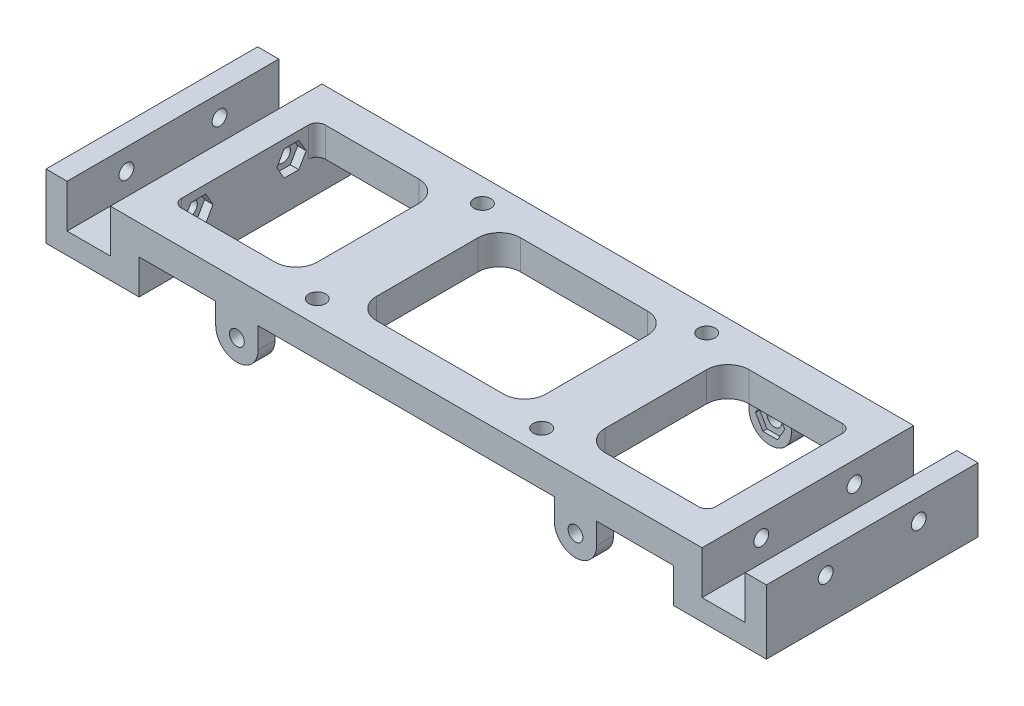
SolidWorks part; units mm, degrees
note: The reader was unsure of these and kept them because the rebuilt part matched: shared geometry of "Szkic5<2>".
material "ABS"
ref_plane "Płaszczyzna przednia" through (0, 0, 0) normal (0, 0, 1) x (1, 0, 0)
ref_plane "Płaszczyzna górna" through (0, 0, 0) normal (0, 1, 0) x (1, 0, 0)
ref_plane "Płaszczyzna prawa" through (0, 0, 0) normal (1, 0, 0) x (0, 0, -1)
sketch "Szkic1" plane through (0, 0, 0) normal (0, 0, 1) x (1, 0, 0)
  line L0 (0, 0) -> (0, 47.3092) construction
  line L1 (-80.1, 5.1) -> (-69.9, 5.1)
  line L2 (-80.1, 5.1) -> (-80.1, -5.1)
  line L3 (-80.1, -5.1) -> (-69.9, -5.1)
  line L4 (-69.9, 5.1) -> (-69.9, -5.1)
  line L5 (-80.1, 5.1) -> (-69.9, -5.1) construction
  line L6 (-80.1, -5.1) -> (-69.9, 5.1) construction
  line L7 (69.8998, 5.1002) -> (80.1002, 5.1002)
  line L8 (69.8998, 5.1002) -> (69.8998, -5.1002)
  line L9 (69.8998, -5.1002) -> (80.1002, -5.1002)
  line L10 (80.1002, 5.1002) -> (80.1002, -5.1002)
  line L11 (69.8998, 5.1002) -> (80.1002, -5.1002) construction
  line L12 (69.8998, -5.1002) -> (80.1002, 5.1002) construction
  line L13 (-80.1, 5.1) -> (-85.1, 5.1)
  line L14 (-85.1, 5.1) -> (-85.1, -10.1)
  line L15 (-85.1, -10.1) -> (85.1, -10.1)
  line L16 (85.1, -10.1) -> (85.1, 5.1002)
  line L17 (85.1, 5.1002) -> (80.1002, 5.1002)
  line L18 (-69.9, 5.1) -> (69.8998, 5.1002)
  line L19 (-63.1, -10.1) -> (-63.1, -1.9)
  line L20 (-63.1, -1.9) -> (63.1, -1.9)
  line L21 (63.1, -1.9) -> (63.1, -10.1)
  point P0 (-75, 0)
  point P5 (75, 0)
  dimension "D1" = 10.2
  dimension "D2" = 10.2004
  dimension "D3" = 150
  dimension "D4" = 4.9998
  dimension "D5" = 5
  dimension "D6" = 5
  dimension "D7" = 22
  dimension "D8" = 22
  dimension "D9" = 8.2
extrude "Dodanie-wyciągnięcie1" add sketch "Szkic1" along normal blind 50
sketch "Szkic2" plane through (0, -10.1, 0) normal (0, -1, 0) x (1, 0, 0)
  line L0 (85.1, 25) -> (-85.1, 25) construction
  line L1 (85.1, 50) -> (85.1, 0) construction
  line L2 (-85.1, 50) -> (-85.1, 0) construction
  line L3 (0, 0) -> (0, 66.8326) construction
  circle A0 centre (-26.5, 44.5) radius 2
  circle A1 centre (-26.5, 5.5) radius 2
  circle A2 centre (26.5, 5.5) radius 2
  circle A3 centre (26.5, 44.5) radius 2
  point P10 (24.4989, 5.5)
  dimension "D1" = 4
  dimension "D2" = 39
  dimension "D3" = 53
extrude "Wytnij-wyciągnięcie1" cut sketch "Szkic2" against normal blind 35
sketch "Szkic3" plane through (0, -10.1, 0) normal (0, -1, 0) x (1, 0, 0)
  line L0 (85.1, 25) -> (-85.1, 25) construction
  line L1 (-20, 42) -> (20, 42)
  line L2 (-20, 42) -> (-20, 8)
  line L3 (-20, 8) -> (20, 8)
  line L4 (20, 42) -> (20, 8)
  line L5 (-20, 42) -> (20, 8) construction
  line L6 (-20, 8) -> (20, 42) construction
  line L7 (85.1, 50) -> (85.1, 0) construction
  line L8 (-85.1, 50) -> (-85.1, 0) construction
  line L9 (0, 0) -> (0, 60.021) construction
  line L12 (-63.1, 8) -> (-34, 8)
  line L13 (-63.1, 8) -> (-63.1, 42)
  line L14 (-63.1, 42) -> (-34, 42)
  line L15 (-34, 8) -> (-34, 42)
  line L16 (-63.1, 8) -> (-34, 42) construction
  line L17 (-63.1, 42) -> (-34, 8) construction
  line L18 (34, 8) -> (63.1, 8)
  line L19 (34, 8) -> (34, 42)
  line L20 (34, 42) -> (63.1, 42)
  line L21 (63.1, 8) -> (63.1, 42)
  line L22 (34, 8) -> (63.1, 42) construction
  line L23 (34, 42) -> (63.1, 8) construction
  point P0 (0, 25)
  point P13 (0, 0)
  point P14 (0, 0)
  point P16 (48.55, 25)
  point P17 (0, 25)
  point P18 (-48.55, 25)
  dimension "D1" = 34
  dimension "D2" = 40
  dimension "D4" = 29.1
  dimension "D6" = 29.1
  dimension "D7" = 14
  dimension "D8" = 14
extrude "Wytnij-wyciągnięcie2" cut sketch "Szkic3" against normal blind 35
sketch "Szkic4" plane through (85.1, 0, 0) normal (1, 0, 0) x (0, 0, -1)
  line L0 (-25, -10.1) -> (-25, 5.1002) construction
  line L1 (-50, -10.1) -> (0, -10.1) construction
  line L2 (-50, 5.1002) -> (0, 5.1002) construction
  circle A0 centre (-36, 0.1002) radius 1.75
  circle A1 centre (-14, 0.1002) radius 1.75
  dimension "D1" = 3.5
  dimension "D2" = 22
  dimension "D3" = 5
extrude "Wytnij-wyciągnięcie3" cut sketch "Szkic4" against normal blind 35
sketch "Szkic5" plane through (85.1, 0, 0) normal (1, 0, 0) x (0, 0, -1)
  line L1 (-34.2679, 3.1002) -> (-37.7321, 3.1002)
  line L2 (-37.7321, 3.1002) -> (-39.4641, 0.1002)
  line L3 (-39.4641, 0.1002) -> (-37.7321, -2.8998)
  line L4 (-37.7321, -2.8998) -> (-34.2679, -2.8998)
  line L5 (-34.2679, -2.8998) -> (-32.5359, 0.1002)
  line L6 (-32.5359, 0.1002) -> (-34.2679, 3.1002)
  line L7 (-12.2679, 3.1002) -> (-15.7321, 3.1002)
  line L8 (-15.7321, 3.1002) -> (-17.4641, 0.1002)
  line L9 (-17.4641, 0.1002) -> (-15.7321, -2.8998)
  line L10 (-15.7321, -2.8998) -> (-12.2679, -2.8998)
  line L11 (-12.2679, -2.8998) -> (-10.5359, 0.1002)
  line L12 (-10.5359, 0.1002) -> (-12.2679, 3.1002)
  circle A0 centre (-36, 0.1002) radius 3 construction
  circle A1 centre (-14, 0.1002) radius 3 construction
  dimension "D1" = 6
extrude "Wytnij-wyciągnięcie4" cut sketch "Szkic5" along normal blind 2 from surface at -22 starting at face at (63.1, 0.1002, 34.25)
mirror "Lustro1" about plane through (0, 0, 0) normal (1, 0, 0) of "Wytnij-wyciągnięcie3"
extrude "Wytnij-wyciągnięcie5" cut sketch "Szkic5<2>" against normal blind 2 from surface at -148.2 starting at face at (-63.1, 0.1002, 37.75)
sketch "Szkic5<2>" plane through (85.1, 0, 0) normal (1, 0, 0) x (0, 0, -1) same geometry as "Szkic5"
sketch "Szkic7" plane through (0, 0, 50) normal (0, 0, 1) x (1, 0, 0)
  line L0 (-63.1, -1.9) -> (63.1, -1.9) construction
  line L3 (-34.9999, -6.9) -> (-34.9999, -1.9)
  line L4 (-44.9999, -6.9) -> (-44.9999, -1.9)
  line L5 (35.0001, -6.9) -> (35.0001, -1.9)
  line L6 (45.0001, -6.9) -> (45.0001, -1.9)
  line L7 (-63.1, -1.9) -> (63.1, -1.9)
  line L8 (0, -1.9) -> (-0.0001, 5.1001) construction
  line L9 (-69.9, 5.1) -> (69.8998, 5.1002) construction
  circle A4 centre (-39.9999, -6.9) radius 5
  circle A5 centre (40.0001, -6.9) radius 5
  circle A6 centre (-39.9999, -6.9) radius 1.75
  circle A7 centre (40.0001, -6.9) radius 1.75
  point P8 (-39.0618, -6.9)
  point P21 (0, 0)
  point P22 (0, 0)
  dimension "D1" = 10
  dimension "D3" = 5
  dimension "D4" = 5
  dimension "D5" = 80
  dimension "D2" = 3.5
  dimension "D6" = 40
extrude "Dodanie-wyciągnięcie4" add sketch "Szkic7" against normal blind 4
sketch "Szkic8" plane through (0, 0, 46) normal (0, 0, -1) x (-1, 0, 0)
  line L1 (43.464, -6.9) -> (41.732, -3.9)
  line L2 (41.732, -3.9) -> (38.2679, -3.9)
  line L3 (38.2679, -3.9) -> (36.5358, -6.9)
  line L4 (36.5358, -6.9) -> (38.2679, -9.9)
  line L5 (38.2679, -9.9) -> (41.732, -9.9)
  line L6 (41.732, -9.9) -> (43.464, -6.9)
  line L7 (-36.536, -6.9) -> (-38.268, -3.9)
  line L8 (-38.268, -3.9) -> (-41.7321, -3.9)
  line L9 (-41.7321, -3.9) -> (-43.4642, -6.9)
  line L10 (-43.4642, -6.9) -> (-41.7321, -9.9)
  line L11 (-41.7321, -9.9) -> (-38.268, -9.9)
  line L12 (-38.268, -9.9) -> (-36.536, -6.9)
  circle A0 centre (39.9999, -6.9) radius 3 construction
  circle A1 centre (-40.0001, -6.9) radius 3 construction
  dimension "D1" = 6
extrude "Wytnij-wyciągnięcie6" cut sketch "Szkic8" against normal blind 1
ref_plane "Płaszczyzna1" through (0, 0, 25) normal (0, 0, -1) x (-1, 0, 0)
mirror "Lustro3" about plane through (0, 0, 25) normal (0, 0, -1) of "Wytnij-wyciągnięcie6", "Dodanie-wyciągnięcie4"
fillet "Zaokrąglenie1" radius 2 4 edges at (63.1, 1.6001, 42) (63.1, 1.6001, 8) (-63.1, 1.6, 8) (-63.1, 1.6, 42)
fillet "Zaokrąglenie2" radius 5 8 edges at (-34, 1.6, 42) (-34, 1.6, 8) (-20, 1.6, 8) (-20, 1.6, 42) (34, 1.6001, 42) (34, 1.6001, 8) (20, 1.6001, 42) (20, 1.6001, 8)
